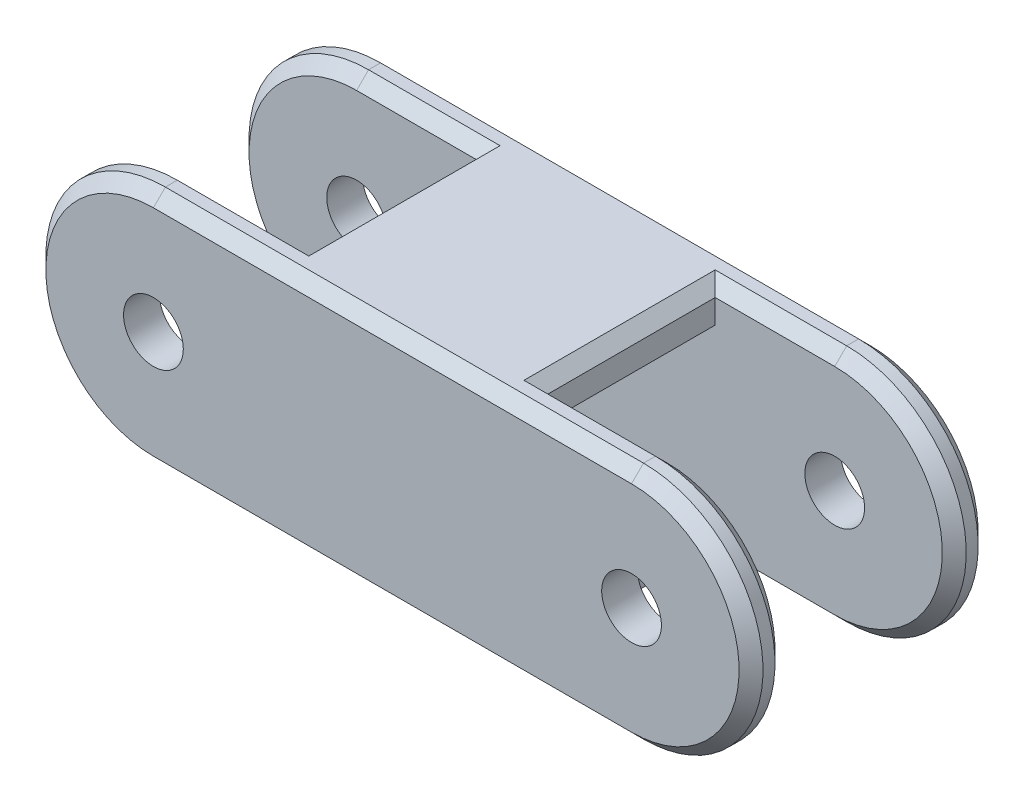
SolidWorks part; units mm, degrees
ref_plane "Front Plane" through (0, 0, 0) normal (0, 0, 1) x (1, 0, 0)
ref_plane "Top Plane" through (0, 0, 0) normal (0, 1, 0) x (1, 0, 0)
ref_plane "Right Plane" through (0, 0, 0) normal (1, 0, 0) x (0, 0, -1)
sketch "Sketch1" plane through (0, 0, 0) normal (0, 0, 1) x (1, 0, 0)
  line L0 (-20, 0) -> (20, 0) construction
  line L1 (-20, 10) -> (20, 10)
  line L2 (-20, -10) -> (20, -10)
  arc A0 (-20, 10) -> (-20, -10) centre (-20, 0) ccw
  arc A1 (20, -10) -> (20, 10) centre (20, 0) ccw
  point P3 (0, 0)
  dimension "D1" = 20
  dimension "D2" = 40
extrude "Boss-Extrude1" add sketch "Sketch1" along normal mid plane 20
sketch "Sketch2" plane through (0, 0, 0) normal (0, 0, 1) x (1, 0, 0)
  line L0 (-20, 10) -> (-10, 10)
  line L1 (-10, 10) -> (-10, -10)
  line L2 (-10, -10) -> (-20, -10)
  line L3 (0, 10) -> (0, -10) construction
  line L4 (10, -10) -> (20, -10)
  line L5 (10, 10) -> (10, -10)
  line L6 (20, 10) -> (10, 10)
  arc A0 (-20, 10) -> (-20, -10) centre (-20, 0) ccw
  arc A1 (20, 10) -> (20, -10) centre (20, 0) cw
  dimension "D1" = 20
extrude "Cut-Extrude1" cut sketch "Sketch2" against normal mid plane 14
sketch "Sketch3" plane through (0, 0, 0) normal (0, 0, 1) x (1, 0, 0)
  line L0 (0, 10) -> (0, -10) construction
  line L1 (20, 10) -> (-20, 10) construction
  line L2 (-20, -10) -> (20, -10) construction
  circle A0 centre (-20, 0) radius 2.5
  circle A1 centre (20, 0) radius 2.5
  dimension "D1" = 5
extrude "Cut-Extrude2" cut sketch "Sketch3" against normal mid plane 20
chamfer "Chamfer2" distance 1 angle 45 12 edges at (15, -10, -7) (30, 0, -7) (15, 10, -7) (15, -10, 7) (30, 0, 7) (15, 10, 7) (-15, -10, 7) (-30, 0, 7) (-15, 10, 7) (-15, -10, -7) (-30, 0, -7) (-15, 10, -7)
chamfer "Chamfer3" distance 1 angle 45 8 edges at (0, -10, -10) (30, 0, -10) (-30, 0, -10) (0, 10, -10) (0, -10, 10) (30, 0, 10) (-30, 0, 10) (0, 10, 10)
shell "Shell1" thickness 3 removed face at (10, 0, 0) removed face at (-10, 0, 0)
chamfer "Chamfer4" distance 1 angle 45 4 edges at (10, -10, 0) (10, 10, 0) (-10, -10, 0) (-10, 10, 0)
